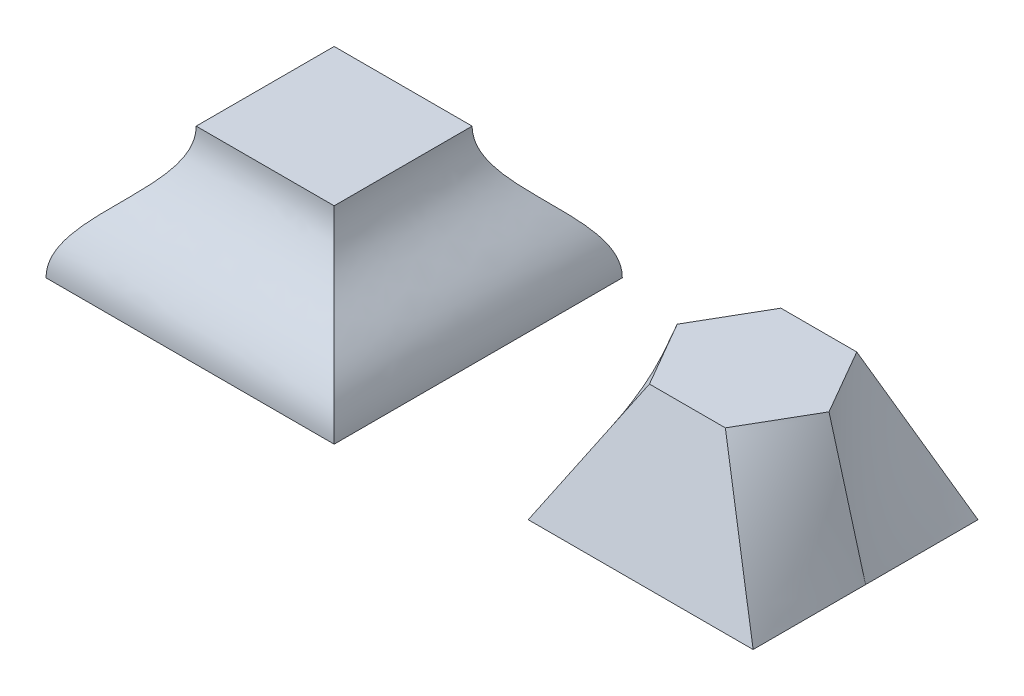
SolidWorks part; units mm, degrees
ref_plane "Front Plane" through (0, 0, 0) normal (0, 0, 1) x (1, 0, 0)
ref_plane "Top Plane" through (0, 0, 0) normal (0, 1, 0) x (1, 0, 0)
ref_plane "Right Plane" through (0, 0, 0) normal (1, 0, 0) x (0, 0, -1)
sketch "Sketch1" plane through (0, 0, 0) normal (0, 1, 0) x (1, 0, 0)
  line L6 (38.3807, -38.3807) -> (-38.3807, -38.3807)
  line L7 (38.3807, -38.3807) -> (38.3807, 38.3807)
  line L8 (38.3807, 38.3807) -> (-38.3807, 38.3807)
  line L9 (-38.3807, -38.3807) -> (-38.3807, 38.3807)
  line L10 (38.3807, -38.3807) -> (-38.3807, 38.3807) construction
  line L11 (38.3807, 38.3807) -> (-38.3807, -38.3807) construction
  point P0 (0, 0)
sketch "Sketch2" plane through (0, 0, 0) normal (0, 0, 1) x (1, 0, 0)
  line L0 (38.3807, 0) -> (49.5272, 15.7907)
  line L1 (38.3807, 0) -> (-38.3807, 0) construction
ref_plane "Plane1" through (0, 35, 0) normal (0, 1, 0) x (1, 0, 0)
sketch "Sketch3" plane through (0, 35, 0) normal (0, 1, 0) x (1, 0, 0)
  line L0 (38.3807, 38.3807) -> (-38.3807, -38.3807) construction
  line L1 (-18.3807, -18.3807) -> (18.3807, -18.3807)
  line L2 (-18.3807, -18.3807) -> (-18.3807, 18.3807)
  line L3 (-18.3807, 18.3807) -> (18.3807, 18.3807)
  line L4 (18.3807, -18.3807) -> (18.3807, 18.3807)
  line L5 (-18.3807, -18.3807) -> (18.3807, 18.3807) construction
  line L6 (-18.3807, 18.3807) -> (18.3807, -18.3807) construction
  line L7 (38.3807, -38.3807) -> (38.3807, 38.3807) construction
  point P0 (0, 0)
  dimension "D1" = 20
loft "Loft1" add profiles "Sketch1", "Sketch3" start constraint normal to profile start tangent length 1 end constraint normal to profile end tangent length 1 connector at (-38.3807, 0, 38.3807) connector at (-18.3807, 35, 18.3807)
sketch "Sketch5" plane through (0, 0, 0) normal (0, 1, 0) x (1, 0, 0)
  line L0 (81.6499, 0) -> (141.5558, 0) construction
  line L1 (141.5558, -29.9529) -> (81.6499, -29.9529)
  line L2 (141.5558, -29.9529) -> (141.5558, 29.9529) construction
  line L3 (141.5558, 29.9529) -> (81.6499, 29.9529)
  line L4 (81.6499, -29.9529) -> (81.6499, 29.9529) construction
  line L5 (141.5558, -29.9529) -> (81.6499, 29.9529) construction
  line L6 (141.5558, 29.9529) -> (81.6499, -29.9529) construction
  line L7 (81.6499, 29.9529) -> (81.6499, 0)
  line L8 (81.6499, 0) -> (81.6499, -29.9529)
  line L9 (141.5558, -29.9529) -> (141.5558, 0)
  line L10 (141.5558, 0) -> (141.5558, 29.9529)
  point P0 (111.6029, 0)
sketch "Sketch7" plane through (0, 35, 0) normal (0, 1, 0) x (1, 0, 0)
  line L0 (141.5558, -29.9529) -> (81.6499, 29.9529) construction
  line L1 (91.3858, 0) -> (101.4943, -17.5085)
  line L2 (101.4943, -17.5085) -> (121.7114, -17.5085)
  line L3 (121.7114, -17.5085) -> (131.82, 0)
  line L4 (131.82, 0) -> (121.7114, 17.5085)
  line L5 (121.7114, 17.5085) -> (101.4943, 17.5085)
  line L6 (101.4943, 17.5085) -> (91.3858, 0)
  line L7 (81.6499, 0) -> (141.5558, 0) construction
  circle A0 centre (111.6029, 0) radius 17.5085 construction
  point P10 (131.6978, 0)
  point P13 (131.82, 0)
loft "Loft2" add profiles "Sketch7", "Sketch5" connector at (121.7114, 35, -17.5085) connector at (141.5558, 0, -29.9529)
